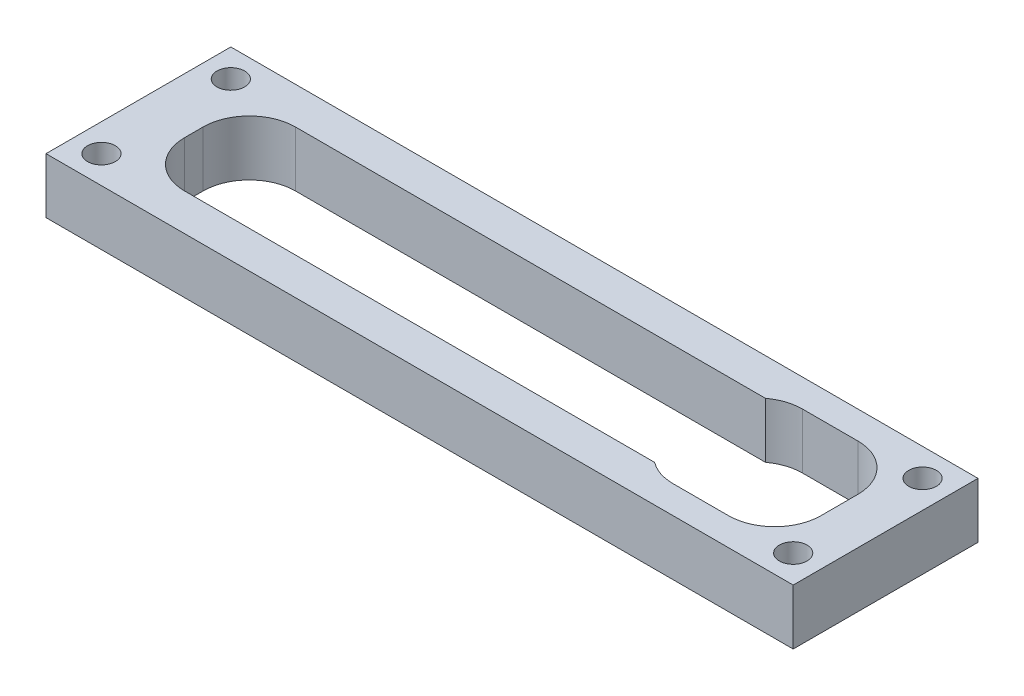
SolidWorks part; units mm, degrees
ref_plane "Front Plane" through (0, 0, 0) normal (0, 0, 1) x (1, 0, 0)
ref_plane "Top Plane" through (0, 0, 0) normal (0, 1, 0) x (1, 0, 0)
ref_plane "Right Plane" through (0, 0, 0) normal (1, 0, 0) x (0, 0, -1)
sketch "Sketch1" plane through (0, 0, 0) normal (0, 1, 0) x (1, 0, 0)
  line L0 (40.4319, 20) -> (40.4319, 0) construction
  line L1 (0, 0) -> (80.8639, 0)
  line L2 (0, 0) -> (0, 20)
  line L3 (0, 20) -> (80.8639, 20)
  line L4 (80.8639, 0) -> (80.8639, 20)
  line L5 (0, 10) -> (80.8639, 10) construction
  line L6 (40.4319, 16) -> (40.4319, 4) construction
  line L7 (6, 16) -> (74.8639, 16)
  line L8 (6, 16) -> (6, 4)
  line L9 (6, 4) -> (74.8639, 4)
  line L10 (74.8639, 16) -> (74.8639, 4)
  line L11 (6, 10) -> (74.8639, 10) construction
  circle A0 centre (3, 17) radius 1.5
  circle A1 centre (3, 3) radius 1.5
  circle A2 centre (77.8639, 3) radius 1.5
  circle A3 centre (77.8639, 17) radius 1.5
  point P17 (40.4319, 10)
  point P18 (40.4319, 10)
  dimension "D7" = 3
  dimension "D1" = 80.8639
  dimension "D2" = 20
  dimension "D3" = 68.8639
  dimension "D4" = 12
  dimension "D5" = 3
  dimension "D6" = 3
extrude "Boss-Extrude1" add sketch "Sketch1" along normal blind 6
sketch "Sketch2" plane through (0, 6, 0) normal (0, 1, 0) x (1, 0, 0)
  line L0 (92, 10) -> (-49908, 10) construction
  line L1 (74.8639, 4) -> (74.8639, 16) construction
  line L2 (61.8639, 17) -> (61.8639, 16)
  line L5 (74.8639, 16) -> (6, 16) construction
  line L6 (68.8639, 17) -> (68.8639, 3) construction
  line L7 (61.8639, 17) -> (75.8639, 17)
  line L9 (61.8639, 3) -> (75.8639, 3)
  line L10 (75.8639, 17) -> (75.8639, 3)
  line L12 (61.8639, 16) -> (74.8639, 16)
  line L13 (74.8639, 16) -> (74.8639, 4)
  line L14 (74.8639, 4) -> (61.8639, 4)
  line L15 (6, 4) -> (74.8639, 4) construction
  line L16 (61.8639, 4) -> (61.8639, 3)
  point P4 (74.8639, 10)
  point P23 (68.8639, 10)
  dimension "D1" = 1
  dimension "D2" = 14
  dimension "D3" = 14
extrude "Cut-Extrude1" cut sketch "Sketch2" against normal through all
fillet "Fillet1" radius 5 6 edges at (75.8639, 3, -17) (75.8639, 3, -3) (61.8639, 3, -17) (61.8639, 3, -3) (6, 3, -4) (6, 3, -16)
equation "\"TrackLength\"= ( ( \"n\" * 28 ) ) / cos ( \"MountAngle\" ) - ( 2 * \"x\" )"
equation "\"D1@Sketch1\"=\"TrackLength\""
equation "\"TrackWidth\"= \"MarbleTrackWidth\" + ( 2 * 4 )"
equation "\"D2@Sketch1\"=\"TrackWidth\""
equation "\"MarbleTrackWidth\"= \"MarbleWidth\" - 1"
equation "\"MarbleTrackLength\"= \"TrackLength\" - ( 2 * 6 )"
equation "\"D3@Sketch1\"=\"MarbleTrackLength\""
equation "\"D4@Sketch1\"=\"MarbleTrackWidth\""
equation "\"MarbleWidth\"= 13"
equation "\"n\"= 3"
equation "\"MountAngle\"= 10"
equation "\"x\" = 14 / cos ( \"MountAngle\" ) - 12"
